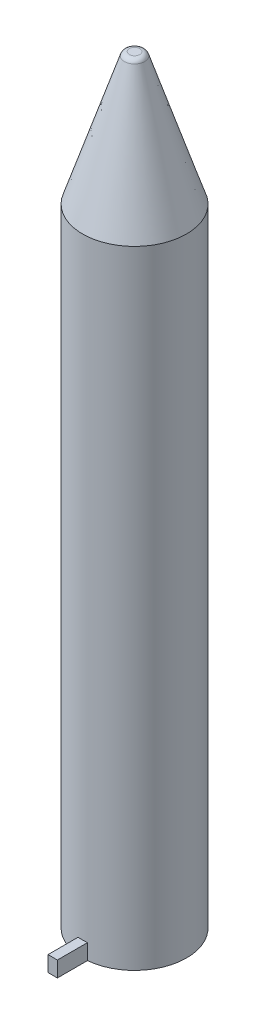
SolidWorks part; units mm, degrees
ref_plane "Front Plane" through (0, 0, 0) normal (0, 0, 1) x (1, 0, 0)
ref_plane "Top Plane" through (0, 0, 0) normal (0, 1, 0) x (1, 0, 0)
ref_plane "Right Plane" through (0, 0, 0) normal (1, 0, 0) x (0, 0, -1)
sketch "Sketch1" plane through (0, 0, 0) normal (0, 1, 0) x (1, 0, 0)
  circle A0 centre (0, 0) radius 10
  dimension "D1" = 20
extrude "Boss-Extrude1" add sketch "Sketch1" along normal blind 120.65
sketch "Sketch2" plane through (0, 0, 0) normal (0, 0, 1) x (1, 0, 0)
  line L8 (0, 120.65) -> (0, 146.05)
  line L9 (10, 120.65) -> (-10, 120.65) construction
  line L10 (1.9508, 145.3597) -> (10, 120.65)
  line L11 (10, 120.65) -> (0, 120.65)
  line L12 (1, 146.05) -> (0, 146.05)
  arc A3 (1, 146.05) -> (1.9508, 145.3597) centre (1, 145.05) cw
  dimension "D2" = 25.4
  dimension "D1" = 1
revolve "Revolve1" add sketch "Sketch2" angle 360 about L8
sketch "Sketch3" plane through (0, 0, 0) normal (0, -1, 0) x (1, 0, 0)
  line L1 (-0.9, 15.75) -> (0.9, 15.75)
  line L2 (-0.9, 15.75) -> (-0.9, 9.3548)
  line L4 (0.9, 15.75) -> (0.9, 9.3548)
  arc A0 (0.9, 9.3548) -> (-0.9, 9.3548) centre (0, 0) ccw
  dimension "D1" = 0.9
  dimension "D3" = 15.75
extrude "Boss-Extrude2" add sketch "Sketch3" against normal blind 3
sketch "Sketch4" plane through (0, 0, 0) normal (0, -1, 0) x (1, 0, 0)
  circle A0 centre (0, 0) radius 6.25
  dimension "D1" = 12.5
extrude "Cut-Extrude1" cut sketch "Sketch4" against normal blind 4
